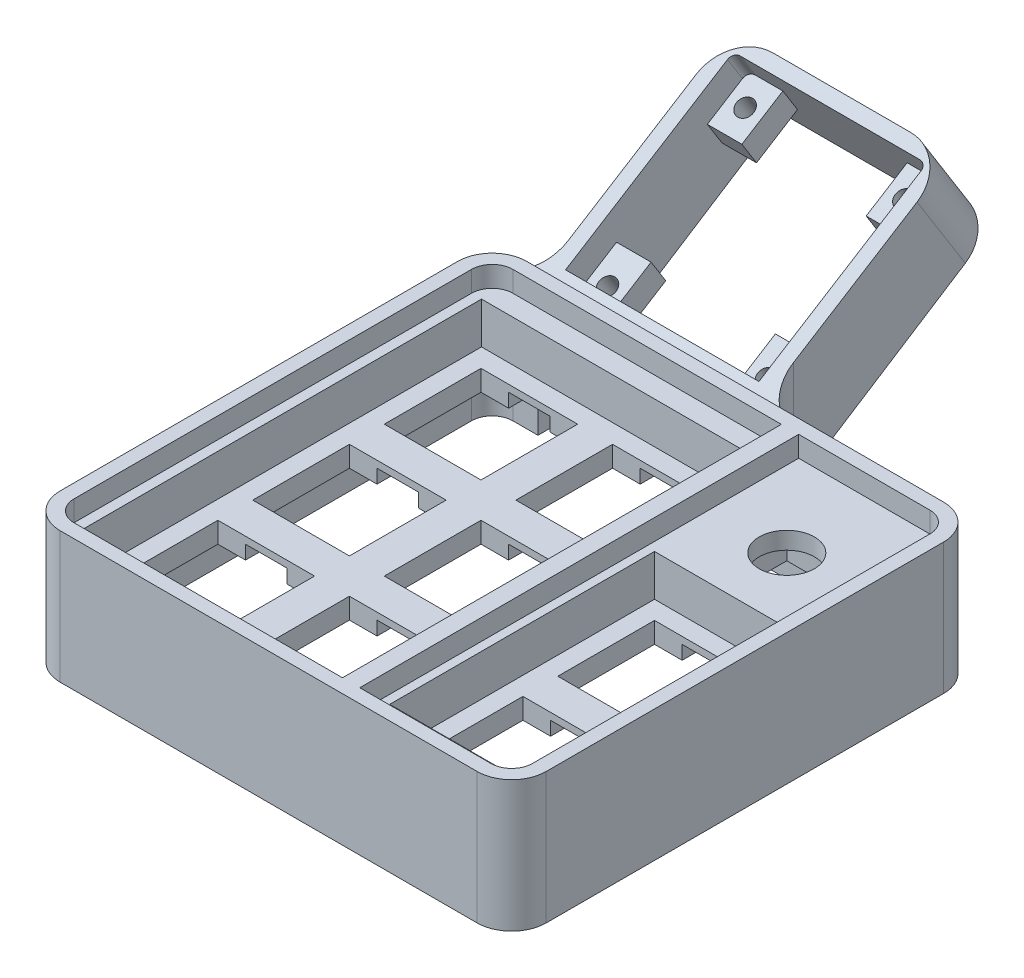
SolidWorks part; units mm, degrees
ref_plane "Ebene vorne" through (0, 0, 0) normal (0, 0, 1) x (1, 0, 0)
ref_plane "Ebene oben" through (0, 0, 0) normal (0, 1, 0) x (1, 0, 0)
ref_plane "Ebene rechts" through (0, 0, 0) normal (1, 0, 0) x (0, 0, -1)
sketch "Skizze1" plane through (0, 0, 0) normal (0, 1, 0) x (1, 0, 0)
  line L0 (-33.9289, -4.0378) -> (-33.9289, -11.968) construction
  line L1 (-59.9789, 36.498) -> (-45.9789, 36.498)
  line L2 (-59.9789, 36.498) -> (-59.9789, 22.498)
  line L3 (-59.9789, 22.498) -> (-45.9789, 22.498)
  line L4 (-45.9789, 36.498) -> (-45.9789, 22.498)
  line L5 (-40.9289, 36.498) -> (-26.9289, 36.498)
  line L6 (-40.9289, 36.498) -> (-40.9289, 22.498)
  line L7 (-40.9289, 22.498) -> (-26.9289, 22.498)
  line L8 (-26.9289, 36.498) -> (-26.9289, 22.498)
  line L9 (-59.9789, 17.448) -> (-45.9789, 17.448)
  line L10 (-59.9789, 17.448) -> (-59.9789, 3.448)
  line L11 (-59.9789, 3.448) -> (-45.9789, 3.448)
  line L12 (-45.9789, 17.448) -> (-45.9789, 3.448)
  line L13 (-40.9289, 17.448) -> (-26.9289, 17.448)
  line L14 (-40.9289, 17.448) -> (-40.9289, 3.448)
  line L15 (-40.9289, 3.448) -> (-26.9289, 3.448)
  line L16 (-26.9289, 17.448) -> (-26.9289, 3.448)
  line L17 (-15.8039, 3.448) -> (-1.8039, 3.448)
  line L18 (-15.8039, 3.448) -> (-15.8039, 17.448)
  line L19 (-15.8039, 17.448) -> (-1.8039, 17.448)
  line L20 (-1.8039, 3.448) -> (-1.8039, 17.448)
  line L21 (-59.9789, -15.602) -> (-45.9789, -15.602)
  line L22 (-59.9789, -15.602) -> (-59.9789, -1.602)
  line L23 (-59.9789, -1.602) -> (-45.9789, -1.602)
  line L24 (-45.9789, -15.602) -> (-45.9789, -1.602)
  line L25 (-40.9289, -15.602) -> (-26.9289, -15.602)
  line L26 (-40.9289, -15.602) -> (-40.9289, -1.602)
  line L27 (-40.9289, -1.602) -> (-26.9289, -1.602)
  line L28 (-26.9289, -15.602) -> (-26.9289, -1.602)
  line L29 (-15.8039, -15.602) -> (-1.8039, -15.602)
  line L30 (-15.8039, -15.602) -> (-15.8039, -1.602)
  line L31 (-15.8039, -1.602) -> (-1.8039, -1.602)
  line L32 (-1.8039, -15.602) -> (-1.8039, -1.602)
  line L33 (-66.0789, 44.223) -> (4.2961, 44.223)
  line L34 (-66.0789, 44.223) -> (-66.0789, -23.332)
  line L35 (-66.0789, -23.332) -> (4.2961, -23.332)
  line L36 (4.2961, 44.223) -> (4.2961, -23.332)
  line L37 (-8.8039, -2.5984) -> (-8.8039, -10.451) construction
  line L38 (-52.9789, -1.8609) -> (-52.9789, -10.0378) construction
  dimension "D1" = 14
  dimension "D2" = 14
  dimension "D3" = 5.05
  dimension "D4" = 5.05
  dimension "D5" = 5.05
  dimension "D6" = 11.125
  dimension "D7" = 7.725
  dimension "D8" = 6.1
  dimension "D9" = 7.73
  dimension "D10" = 6.1
extrude "Aufsatz-Linear austragen1" add sketch "Skizze1" along normal blind 3
sketch "Skizze2" plane through (0, 3, 0) normal (0, 1, 0) x (1, 0, 0)
  line L1 (-66.0789, 44.223) -> (4.2961, 44.223)
  line L2 (-66.0789, 44.223) -> (-66.0789, -23.332)
  line L3 (-66.0789, -23.332) -> (4.2961, -23.332)
  line L4 (4.2961, 44.223) -> (4.2961, -23.332)
  line L5 (-64.0789, 42.223) -> (2.2961, 42.223)
  line L6 (-64.0789, 42.223) -> (-64.0789, -21.332)
  line L7 (-64.0789, -21.332) -> (2.2961, -21.332)
  line L8 (2.2961, 42.223) -> (2.2961, -21.332)
  dimension "D1" = 2
  dimension "D2" = 2
  dimension "D3" = 2
  dimension "D4" = 2
extrude "Aufsatz-Linear austragen2" add sketch "Skizze2" along normal blind 9
sketch "Skizze3" plane through (0, 3, 0) normal (0, 1, 0) x (1, 0, 0)
  line L0 (2.2961, 42.223) -> (-64.0789, 42.223) construction
  line L1 (-22.2039, 42.223) -> (-19.7039, 42.223)
  line L2 (-22.2039, 42.223) -> (-22.2039, -21.332)
  line L3 (-22.2039, -21.332) -> (-19.7039, -21.332)
  line L4 (-19.7039, 42.223) -> (-19.7039, -21.332)
  line L5 (-64.0789, -21.332) -> (2.2961, -21.332) construction
  line L6 (4.2961, -23.332) -> (4.2961, 44.223) construction
  dimension "D1" = 2.5
  dimension "D2" = 24
extrude "Aufsatz-Linear austragen3" add sketch "Skizze3" along normal up to surface (9 mm away) up to face at (-30.8914, 12, -10.4455)
sketch "Skizze4" plane through (0, 3, 0) normal (0, 1, 0) x (1, 0, 0)
  line L0 (-22.2039, 42.223) -> (-22.2039, -21.332) construction
  line L1 (-62.6289, 39.223) -> (-23.4539, 39.223)
  line L2 (-62.6289, 39.223) -> (-62.6289, -18.332)
  line L3 (-62.6289, -18.332) -> (-23.4539, -18.332)
  line L4 (-23.4539, 39.223) -> (-23.4539, -18.332)
  line L5 (-66.0789, -23.332) -> (4.2961, -23.332) construction
  line L7 (4.2961, 44.223) -> (-66.0789, 44.223) construction
  line L8 (-64.0789, 42.223) -> (-64.0789, -21.332) construction
  line L9 (-64.0789, 42.223) -> (-22.2039, 42.223)
  line L10 (-64.0789, 42.223) -> (-64.0789, -21.332)
  line L11 (-64.0789, -21.332) -> (-22.2039, -21.332)
  line L12 (-22.2039, 42.223) -> (-22.2039, -21.332)
  dimension "D1" = 1.25
  dimension "D2" = 5
  dimension "D3" = 1.45
  dimension "D4" = 5
extrude "Aufsatz-Linear austragen4" add sketch "Skizze4" along normal offset from surface (6 mm away) 3 up to face at (-8.7039, 12, -10.4455)
sketch "Skizze5" plane through (0, 3, 0) normal (0, 1, 0) x (1, 0, 0)
  line L0 (-1.8039, 17.448) -> (-15.8039, 17.448) construction
  line L1 (-18.4539, 20.098) -> (0.8461, 20.098)
  line L2 (-18.4539, 20.098) -> (-18.4539, -18.252)
  line L3 (-18.4539, -18.252) -> (0.8461, -18.252)
  line L4 (0.8461, 20.098) -> (0.8461, -18.252)
  line L5 (-1.8039, 3.448) -> (-1.8039, 17.448) construction
  line L6 (-15.8039, -15.602) -> (-1.8039, -15.602) construction
  line L7 (-15.8039, -1.602) -> (-15.8039, -15.602) construction
  line L9 (-19.7039, 42.223) -> (2.2961, 42.223)
  line L10 (-19.7039, 42.223) -> (-19.7039, -21.332)
  line L11 (-19.7039, -21.332) -> (2.2961, -21.332)
  line L12 (2.2961, 42.223) -> (2.2961, -21.332)
  dimension "D1" = 2.65
  dimension "D2" = 2.65
  dimension "D3" = 2.65
  dimension "D4" = 2.65
extrude "Aufsatz-Linear austragen5" add sketch "Skizze5" along normal offset from surface (6 mm away) 3 up to face at (-8.7039, 12, -10.4455)
sketch "Skizze6" plane through (0, 9, 0) normal (0, 1, 0) x (1, 0, 0)
  line L1 (-8.7039, 37.1976) -> (-8.7039, 23.8687) construction
  line L2 (-19.7039, -21.332) -> (-19.7039, 42.223) construction
  line L3 (2.2961, -21.332) -> (2.2961, 42.223) construction
  line L4 (-14.7078, 29.503) -> (-1.2358, 29.503) construction
  line L5 (4.2961, 44.223) -> (-66.0789, 44.223) construction
  circle A0 centre (-8.7039, 29.503) radius 4
  dimension "D1" = 8
  dimension "D2" = 14.72
extrude "Schnitt-Linear austragen1" cut sketch "Skizze6" against normal through all
sketch "Skizze7" plane through (0, 0, 0) normal (0, -1, 0) x (1, 0, 0)
  line L0 (-8.7039, -29.503) -> (-8.7039, -37.2605) construction
  line L1 (-16.7039, -21.503) -> (-0.7039, -21.503)
  line L2 (-16.7039, -21.503) -> (-16.7039, -37.503)
  line L3 (-16.7039, -37.503) -> (-0.7039, -37.503)
  line L4 (-0.7039, -21.503) -> (-0.7039, -37.503)
  line L5 (-11.6454, -29.503) -> (-3.5978, -29.503) construction
  dimension "D1" = 16
  dimension "D2" = 16
extrude "Schnitt-Linear austragen2" cut sketch "Skizze7" against normal offset from surface (6.5 mm away) 2.5 up to face at (-8.7039, 9, -25.503)
sketch "Skizze8" plane through (0, 0, 0) normal (0, -1, 0) x (1, 0, 0)
  line L1 (-66.0789, 23.332) -> (4.2961, 23.332)
  line L2 (-66.0789, 23.332) -> (-66.0789, -44.223)
  line L3 (-66.0789, -44.223) -> (4.2961, -44.223)
  line L4 (4.2961, 23.332) -> (4.2961, -44.223)
  line L5 (2.2961, -42.223) -> (-64.0789, -42.223)
  line L6 (2.2961, -42.223) -> (2.2961, 21.332)
  line L7 (2.2961, 21.332) -> (-64.0789, 21.332)
  line L8 (-64.0789, -42.223) -> (-64.0789, 21.332)
  dimension "D1" = 2
  dimension "D2" = 2
  dimension "D3" = 2
  dimension "D4" = 2
extrude "Aufsatz-Linear austragen6" add sketch "Skizze8" along normal blind 7
sketch "Skizze14" plane through (0, 0, 0) normal (0, -1, 0) x (1, 0, 0)
  line L0 (-52.9789, 16.4952) -> (-52.9789, -37.7006) construction
  line L1 (-55.9789, 17.602) -> (-49.9789, 17.602)
  line L2 (-55.9789, 17.602) -> (-55.9789, -38.498)
  line L3 (-55.9789, -38.498) -> (-49.9789, -38.498)
  line L4 (-49.9789, 17.602) -> (-49.9789, -38.498)
  line L5 (-36.9289, -38.498) -> (-30.9289, -38.498)
  line L6 (-36.9289, -38.498) -> (-36.9289, 17.602)
  line L7 (-36.9289, 17.602) -> (-30.9289, 17.602)
  line L8 (-30.9289, -38.498) -> (-30.9289, 17.602)
  line L9 (-11.8039, 17.602) -> (-5.8039, 17.602)
  line L10 (-11.8039, 17.602) -> (-11.8039, -19.448)
  line L11 (-11.8039, -19.448) -> (-5.8039, -19.448)
  line L12 (-5.8039, 17.602) -> (-5.8039, -19.448)
  line L13 (-33.9289, -37.009) -> (-33.9289, 19.1358) construction
  line L14 (-8.8039, 20.7076) -> (-8.8039, -19.4677) construction
  line L15 (-59.9789, 1.602) -> (-59.9789, 15.602) construction
  line L16 (-45.9789, 15.602) -> (-45.9789, 1.602) construction
  line L17 (-40.9289, 1.602) -> (-40.9289, 15.602) construction
  line L18 (-26.9289, 15.602) -> (-26.9289, 1.602) construction
  line L19 (-15.8039, 1.602) -> (-15.8039, 15.602) construction
  line L20 (-1.8039, 15.602) -> (-1.8039, 1.602) construction
  line L21 (-59.9789, 15.602) -> (-45.9789, 15.602) construction
  line L22 (-45.9789, -36.498) -> (-59.9789, -36.498) construction
  line L23 (-1.8039, -17.448) -> (-15.8039, -17.448) construction
  dimension "D1" = 6
  dimension "D2" = 2
  dimension "D3" = 2
  dimension "D4" = 2
extrude "Schnitt-Linear austragen8" cut sketch "Skizze14" against normal blind 2
fillet "Verrundung1" radius 5 4 edges at (4.2961, 2.5, -44.223) (4.2961, 2.5, 23.332) (-66.0789, 2.5, 23.332) (-66.0789, 2.5, -44.223)
sketch "Skizze17" plane through (0, 12, 0) normal (0, 1, 0) x (1, 0, 0)
  line L8 (-61.0789, -21.332) -> (-0.7039, -21.332)
  line L9 (2.2961, -18.332) -> (2.2961, 39.223)
  line L10 (-0.7039, 42.223) -> (-61.0789, 42.223)
  line L11 (-64.0789, 39.223) -> (-64.0789, -18.332)
  line L12 (-61.0789, -21.332) -> (-0.7039, -21.332)
  line L13 (2.2961, -18.332) -> (2.2961, 39.223)
  line L14 (-0.7039, 42.223) -> (-61.0789, 42.223)
  line L15 (-64.0789, 39.223) -> (-64.0789, -18.332)
  line L20 (-61.0789, -23.332) -> (-0.7039, -23.332)
  line L21 (4.2961, -18.332) -> (4.2961, 39.223)
  line L22 (-0.7039, 44.223) -> (-61.0789, 44.223)
  line L23 (-66.0789, 39.223) -> (-66.0789, -18.332)
  line L24 (-61.0789, -23.332) -> (-0.7039, -23.332)
  line L25 (4.2961, -18.332) -> (4.2961, 39.223)
  line L26 (-0.7039, 44.223) -> (-61.0789, 44.223)
  line L27 (-66.0789, 39.223) -> (-66.0789, -18.332)
  arc A4 (-0.7039, -21.332) -> (2.2961, -18.332) centre (-0.7039, -18.332) ccw
  arc A6 (-0.7039, -21.332) -> (2.2961, -18.332) centre (-0.7039, -18.332) ccw
  arc A8 (2.2961, 39.223) -> (-0.7039, 42.223) centre (-0.7039, 39.223) ccw
  arc A9 (2.2961, 39.223) -> (-0.7039, 42.223) centre (-0.7039, 39.223) ccw
  arc A10 (-61.0789, 42.223) -> (-64.0789, 39.223) centre (-61.0789, 39.223) ccw
  arc A11 (-61.0789, 42.223) -> (-64.0789, 39.223) centre (-61.0789, 39.223) ccw
  arc A16 (-64.0789, -18.332) -> (-61.0789, -21.332) centre (-61.0789, -18.332) ccw
  arc A18 (-64.0789, -18.332) -> (-61.0789, -21.332) centre (-61.0789, -18.332) ccw
  arc A20 (-0.7039, -23.332) -> (4.2961, -18.332) centre (-0.7039, -18.332) ccw
  arc A22 (-0.7039, -23.332) -> (4.2961, -18.332) centre (-0.7039, -18.332) ccw
  arc A28 (4.2961, 39.223) -> (-0.7039, 44.223) centre (-0.7039, 39.223) ccw
  arc A30 (4.2961, 39.223) -> (-0.7039, 44.223) centre (-0.7039, 39.223) ccw
  arc A32 (-61.0789, 44.223) -> (-66.0789, 39.223) centre (-61.0789, 39.223) ccw
  arc A34 (-61.0789, 44.223) -> (-66.0789, 39.223) centre (-61.0789, 39.223) ccw
  arc A36 (-66.0789, -18.332) -> (-61.0789, -23.332) centre (-61.0789, -18.332) ccw
  arc A37 (-66.0789, -18.332) -> (-61.0789, -23.332) centre (-61.0789, -18.332) ccw
  dimension "D1" = 2
  dimension "D2" = 0
extrude "Aufsatz-Linear austragen8" add sketch "Skizze17" against normal up to surface (12 mm away) up to face at (-30.8914, 0, -10.4455)
ref_plane "Ebene1" through (-43.4539, 0, 0) normal (-1, 0, 0) x (0, 0, 1)
sketch "Skizze21" plane through (-43.4539, 0, 0) normal (-1, 0, 0) x (0, 0, 1)
  line L5 (-72.2086, 27.9873) -> (-44.223, 10.5)
  line L6 (-39.223, 12) -> (-44.223, 12) construction
  line L7 (-72.2086, 27.9873) -> (-79.1551, 16.8707)
  line L8 (-79.1551, 16.8707) -> (-44.223, -5.5)
  line L9 (-44.223, -7) -> (-44.223, 12) construction
  line L10 (-44.223, 10.5) -> (-44.223, -5.5)
  dimension "D1" = 122
  dimension "D2" = 1.5
  dimension "D3" = 33
  dimension "D4" = 90
  dimension "D5" = 16
extrude "Aufsatz-Linear austragen10" add sketch "Skizze21" along normal mid plane 32
sketch "Skizze25" plane through (-43.4539, 0, 0) normal (-1, 0, 0) x (0, 0, 1)
  line L22 (-70.1083, 27.5744) -> (-46.223, 22.7963)
  line L23 (-46.223, -7.3068) -> (-84.1839, 5.0487)
  line L26 (-76.4108, 17.4882) -> (-46.223, -1.8442)
  line L27 (-46.223, 9.3914) -> (-71.5724, 25.2314)
  line L28 (-46.223, -1.8442) -> (-46.223, 9.3914)
  line L29 (-71.5724, 25.2314) -> (-76.4108, 17.4882)
  line L32 (-46.223, -7.3068) -> (-46.223, 22.7963)
  line L33 (-70.1083, 27.5744) -> (-84.1839, 5.0487)
  dimension "D1" = 2
extrude "Schnitt-Linear austragen11" cut sketch "Skizze25" against normal mid plane 28
fillet "Verrundung3" radius 6 2 edges at (-27.4539, 22.429, -75.6818) (-59.4539, 22.429, -75.6818)
fillet "Verrundung4" radius 3 4 edges at (-64.0789, -3.5, 21.332) (-64.0789, -3.5, -42.223) (2.2961, -3.5, -42.223) (2.2961, -3.5, 21.332)
sketch "Skizze29" plane through (0, -12.3222, -7.6998) normal (0, 0.848, 0.5299) x (1, 0, 0)
  line L0 (-54.9539, 70.5674) -> (-54.9539, 74.0674) construction
  line L1 (-57.4539, 74.0674) -> (-29.4539, 74.0674) construction
  line L2 (-54.9539, 70.5674) -> (-57.4539, 70.5674) construction
  line L3 (-57.4539, 74.0674) -> (-57.4539, 45.4258) construction
  circle A0 centre (-54.9539, 70.5674) radius 1.25
  circle A1 centre (-31.9539, 70.5674) radius 1.25
  circle A2 centre (-54.9539, 47.0674) radius 1.25
  circle A3 centre (-31.9539, 47.0674) radius 1.25
  dimension "D1" = 2.5
  dimension "D2" = 23
  dimension "D3" = 23.5
  dimension "D4" = 2.5
  dimension "D5" = 3.5
ref_plane "Ebene2" through (0, -15.7992, -9.8725) normal (0, 0.848, 0.5299) x (1, 0, 0)
sketch "Skizze30" plane through (0, -15.7992, -9.8725) normal (0, 0.848, 0.5299) x (1, 0, 0)
  line L0 (-57.4539, 74.0674) -> (-57.4539, 45.4258) construction
  line L17 (-57.4539, 74.0674) -> (-52.4539, 74.0674)
  line L18 (-57.4539, 74.0674) -> (-57.4539, 67.0674)
  line L19 (-57.4539, 67.0674) -> (-52.4539, 67.0674)
  line L20 (-52.4539, 74.0674) -> (-52.4539, 67.0674)
  line L21 (-29.4539, 74.0674) -> (-34.4539, 74.0674)
  line L22 (-29.4539, 74.0674) -> (-29.4539, 67.0674)
  line L23 (-29.4539, 67.0674) -> (-34.4539, 67.0674)
  line L24 (-34.4539, 74.0674) -> (-34.4539, 67.0674)
  line L25 (-29.4539, 44.5674) -> (-34.4539, 44.5674)
  line L26 (-29.4539, 44.5674) -> (-29.4539, 51.5674)
  line L27 (-29.4539, 51.5674) -> (-34.4539, 51.5674)
  line L28 (-34.4539, 44.5674) -> (-34.4539, 51.5674)
  line L29 (-57.4539, 44.5674) -> (-52.4539, 44.5674)
  line L30 (-57.4539, 44.5674) -> (-57.4539, 51.5674)
  line L31 (-57.4539, 51.5674) -> (-52.4539, 51.5674)
  line L32 (-52.4539, 44.5674) -> (-52.4539, 51.5674)
  line L33 (-29.4539, 74.0674) -> (-29.4539, 45.4258) construction
  dimension "D1" = 5
  dimension "D2" = 7
  dimension "D3" = 15.5
extrude "Aufsatz-Linear austragen11" add sketch "Skizze30" against normal blind 4
extrude "Schnitt-Linear austragen14" cut sketch "Skizze29" against normal up to surface and the other way through all up to face at (-43.4539, 5.7864, -61.8469)
fillet "Verrundung5" radius 1 4 edges at (-29.4539, 17.9252, -76.1378) (-57.4539, 17.9252, -76.1378) (-29.4539, 25.189, -71.5989) (-57.4539, 25.189, -71.5989)
hole_wizard "Tap Drill for M2 Tap1" positions "Sketch2" profile "Sketch3" hole size "M2" standard "DIN"
sketch "Sketch2" plane through (0, 0, 0) normal (0, -1, 0) x (-1, 0, 0)
  line L0 (0.7039, -23.332) -> (61.0789, -23.332) construction
  line L1 (-4.2961, 39.223) -> (-4.2961, -18.332) construction
  line L3 (66.0789, -18.332) -> (66.0789, 39.223) construction
  line L4 (61.0789, 44.223) -> (0.7039, 44.223) construction
  point P0 (62.5789, -19.832)
  point P2 (62.5789, 40.723)
  point P4 (-0.7961, 40.723)
  point P6 (-0.7961, -19.832)
  dimension "D1" = 3.5
  dimension "D2" = 3.5
  dimension "D3" = 3.5
  dimension "D4" = 3.5
sketch "Sketch3" plane through (-62.5789, 0, 19.832) normal (1, 0, 0) x (0, 0, -1)
  line L0 (0, 0) -> (0, 6.5408)
  line L1 (0, 6.5408) -> (0.9, 6)
  line L2 (0.9, 6) -> (0.9, 0)
  line L5 (0.9, 0) -> (0, 0)
  line L10 (0, 6.5408) -> (-0.9, 6) construction
  line L11 (0, -6.35) -> (0, 107.95) construction
  dimension "Hole Dia." = 1.8
  dimension "Hole Depth" = 6
  dimension "Drill Angle" = 118
sketch "Sketch4" plane through (0, 0, 0) normal (0, -1, 0) x (1, 0, 0)
  line L0 (-63.5668, 21.3396) -> (-65.3469, 17.332)
  line L1 (-65.3469, 17.332) -> (-60.0789, 17.332)
  line L2 (-60.0789, 17.332) -> (-60.0789, 22.1142)
  line L3 (-60.0789, 22.1142) -> (-63.5668, 21.3396)
  line L4 (-66.0789, 18.332) -> (-66.0789, -39.223) construction
  line L5 (-0.7039, 23.332) -> (-61.0789, 23.332) construction
  line L6 (-1.7039, 21.8998) -> (-1.7039, 17.332)
  line L7 (-1.7039, 17.332) -> (3.4265, 17.332)
  line L8 (3.4265, 17.332) -> (2.6188, 20.6743)
  line L9 (2.6188, 20.6743) -> (-1.7039, 21.8998)
  line L10 (4.2961, -39.223) -> (4.2961, 18.332) construction
  line L11 (-1.7039, -43.3116) -> (-1.7039, -38.223)
  line L12 (-1.7039, -38.223) -> (3.6426, -38.223)
  line L13 (3.6426, -38.223) -> (1.926, -42.0551)
  line L14 (1.926, -42.0551) -> (-1.7039, -43.3116)
  line L16 (-65.1238, -38.223) -> (-60.0789, -38.223)
  line L17 (-60.0789, -38.223) -> (-60.0789, -43.0564)
  line L18 (-60.0789, -43.0564) -> (-64.0795, -41.8278)
  line L19 (-64.0795, -41.8278) -> (-65.1238, -38.223)
  line L20 (-61.0789, -44.223) -> (-0.7039, -44.223) construction
  line L21 (-61.0789, -44.223) -> (-0.7039, -44.223) construction
  circle A0 centre (-62.5789, 19.832) radius 0.9
  circle A1 centre (0.7961, 19.832) radius 0.9
  circle A2 centre (0.7961, -40.723) radius 0.9
  circle A3 centre (-62.5789, -40.723) radius 0.9
  dimension "D1" = 6
  dimension "D2" = 6
  dimension "D3" = 6
  dimension "D4" = 6
  dimension "D5" = 6
  dimension "D6" = 6
  dimension "D7" = 6
  dimension "D8" = 6
extrude "Boss-Extrude1" add sketch "Sketch4" along normal blind 1.5
fillet "Fillet1" radius 3 4 edges at (-1.7039, -0.75, -38.223) (-1.7039, -0.75, 17.332) (-60.0789, -0.75, 17.332) (-60.0789, -0.75, -38.223)
sketch "Sketch6" plane through (0, 0, -44.223) normal (0, 0, -1) x (-1, 0, 0)
  line L0 (61.0789, -7) -> (0.7039, -7) construction
  line L1 (12.5539, -0.2) -> (22.2539, -0.2)
  line L2 (12.5539, -0.2) -> (12.5539, -4.4)
  line L3 (12.5539, -4.4) -> (22.2539, -4.4)
  line L4 (22.2539, -0.2) -> (22.2539, -4.4)
  line L5 (17.4039, -0.2) -> (17.4039, -4.002) construction
  line L6 (-4.2961, -7) -> (-4.2961, 12) construction
  line L8 (4.6221, -2.3) -> (15.68, -2.3) construction
  line L9 (29.4539, 0) -> (57.4539, 0)
  line L10 (29.4539, 0) -> (29.4539, -7)
  line L11 (29.4539, -7) -> (57.4539, -7)
  line L12 (57.4539, 0) -> (57.4539, -7)
  line L13 (60.0789, 0) -> (1.7039, 0) construction
  line L14 (29.4539, -4.2192) -> (29.4539, 11.7497) construction
  line L15 (57.4539, -4.2192) -> (57.4539, 11.7497) construction
  point P18 (57.4539, -7)
  dimension "D1" = 9.7
  dimension "D2" = 4.2
  dimension "D3" = 21.7
  dimension "D4" = 6.8
extrude "Cut-Extrude1" cut sketch "Sketch6" against normal blind 10 and the other way blind 10
fillet "Verrundung6" radius 1 4 edges at (-12.5539, -0.2, -43.223) (-12.5539, -4.4, -43.223) (-22.2539, -4.4, -43.223) (-22.2539, -0.2, -43.223)
fillet "Verrundung7" radius 3 1 edges at (-43.4539, 0, -46.223)
sketch "Skizze32" plane through (0, 0, -44.223) normal (0, 0, -1) x (-1, 0, 0)
  line L24 (23.7539, -3.4) -> (23.7539, -1.2)
  line L25 (13.5539, -5.9) -> (21.2539, -5.9)
  line L26 (11.0539, -1.2) -> (11.0539, -3.4)
  line L27 (21.2539, 1.3) -> (13.5539, 1.3)
  line L28 (23.7539, -3.4) -> (23.7539, -1.2)
  line L29 (13.5539, -5.9) -> (21.2539, -5.9)
  line L30 (11.0539, -1.2) -> (11.0539, -3.4)
  line L31 (21.2539, 1.3) -> (13.5539, 1.3)
  arc A20 (23.7539, -1.2) -> (21.2539, 1.3) centre (21.2539, -1.2) ccw
  arc A21 (21.2539, -5.9) -> (23.7539, -3.4) centre (21.2539, -3.4) ccw
  arc A22 (11.0539, -3.4) -> (13.5539, -5.9) centre (13.5539, -3.4) ccw
  arc A23 (13.5539, 1.3) -> (11.0539, -1.2) centre (13.5539, -1.2) ccw
  arc A24 (23.7539, -1.2) -> (21.2539, 1.3) centre (21.2539, -1.2) ccw
  arc A25 (21.2539, -5.9) -> (23.7539, -3.4) centre (21.2539, -3.4) ccw
  arc A26 (11.0539, -3.4) -> (13.5539, -5.9) centre (13.5539, -3.4) ccw
  arc A27 (13.5539, 1.3) -> (11.0539, -1.2) centre (13.5539, -1.2) ccw
  dimension "D1" = 1.5
extrude "Schnitt-Linear austragen16" cut sketch "Skizze32" against normal offset from surface (1 mm away) 1 up to face at (-10.6206, -2.8333, -42.223)
fillet "Verrundung8" radius 0.6 8 edges at (-23.0217, 0.5678, -44.223) (-23.7539, -2.3, -44.223) (-23.0217, -5.1678, -44.223) (-17.4039, -5.9, -44.223) (-11.7861, -5.1678, -44.223) (-11.0539, -2.3, -44.223) (-11.7861, 0.5678, -44.223) (-17.4039, 1.3, -44.223)
fillet "Verrundung9" radius 5 2 edges at (-27.4539, 2.5, -44.223) (-59.4539, 2.5, -44.223)
